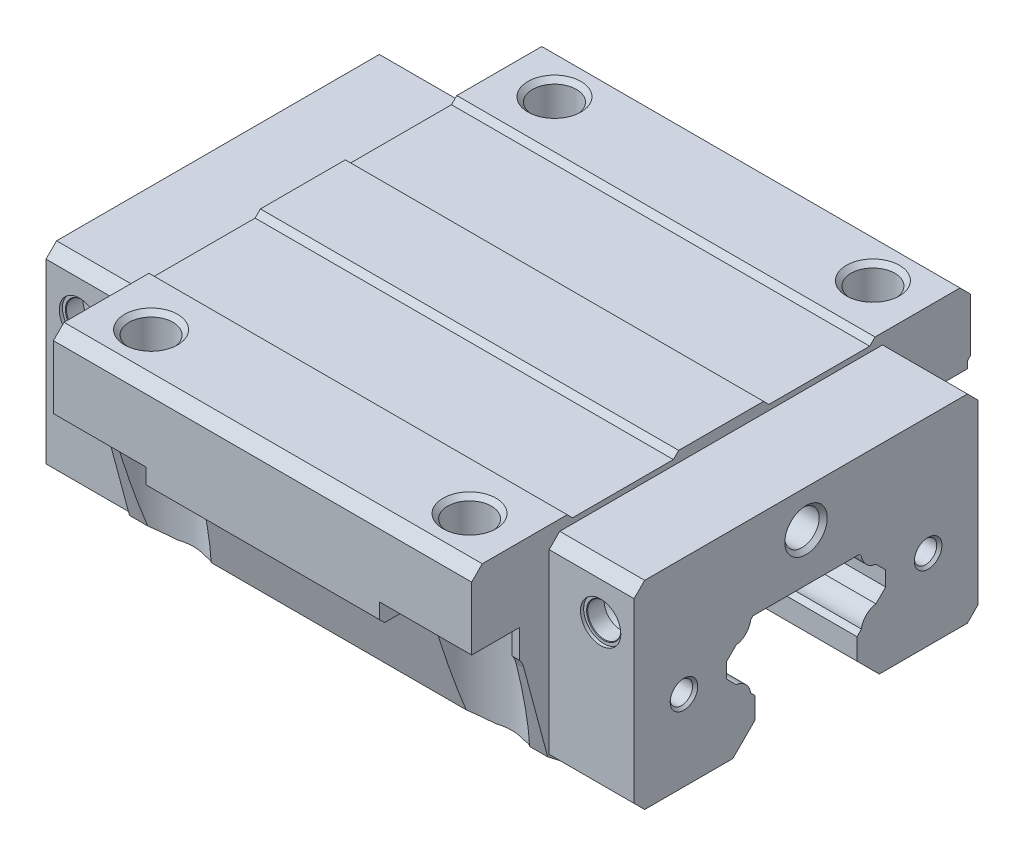
SolidWorks part; units mm, degrees
ref_plane "Спереди" through (0, 0, 0) normal (0, 0, 1) x (1, 0, 0)
ref_plane "Сверху" through (0, 0, 0) normal (0, 1, 0) x (1, 0, 0)
ref_plane "Сбоку" through (0, 0, 0) normal (1, 0, 0) x (0, 0, -1)
ref_plane "Плоскость1" through (0, 0, 0) normal (1, 0, 0) x (0, 0, -1)
sketch "Эскиз1" plane through (0, 0, 0) normal (1, 0, 0) x (0, 0, -1)
  line L0 (-23.5, 18.703) -> (-23.5, 11.2985)
  line L1 (-23.5, 11.2985) -> (-23.0015, 10.8)
  line L2 (-23.0015, 10.8) -> (-20.5347, 10.8)
  line L3 (-18.6028, 9.3176) -> (-16.3361, 0.8584)
  line L4 (-16.3361, 0.8584) -> (-15.2175, 0)
  line L5 (-15.2175, 0) -> (15.2175, 0)
  line L6 (15.2175, 0) -> (16.3361, 0.8584)
  line L7 (16.3361, 0.8584) -> (18.6028, 9.3176)
  line L8 (20.5347, 10.8) -> (22.7015, 10.8)
  line L9 (22.7015, 10.8) -> (23.2, 11.2985)
  line L10 (23.2, 11.2985) -> (23.2, 13.4)
  line L11 (23.2, 13.4) -> (23.5, 13.7)
  line L12 (23.5, 13.7) -> (23.5, 18.703)
  line L13 (23.5, 18.703) -> (22.503, 19.7)
  line L14 (22.503, 19.7) -> (14.5, 19.7)
  line L15 (14.5, 19.7) -> (14, 19.2)
  line L16 (14, 19.2) -> (4.5, 19.2)
  line L17 (4.5, 19.2) -> (4, 19.7)
  line L18 (4, 19.7) -> (-4, 19.7)
  line L19 (-4, 19.7) -> (-4.5, 19.2)
  line L20 (-4.5, 19.2) -> (-14, 19.2)
  line L21 (-14, 19.2) -> (-14.5, 19.7)
  line L22 (-14.5, 19.7) -> (-22.503, 19.7)
  line L23 (-22.503, 19.7) -> (-23.5, 18.703)
  arc A0 (-20.5347, 10.8) -> (-18.6028, 9.3176) centre (-20.5347, 8.8) cw
  arc A1 (18.6028, 9.3176) -> (20.5347, 10.8) centre (20.5347, 8.8) cw
extrude "Бобышка-Вытянуть1" add sketch "Эскиз1" against normal blind 19.7 and the other way blind 19.7
ref_plane "Плоскость2" through (0, 0, 0) normal (1, 0, 0) x (0, 0, -1)
sketch "Эскиз2" plane through (0, 0, 0) normal (1, 0, 0) x (0, 0, -1)
  line L0 (-16.2, 0.997) -> (-15.203, 0)
  line L1 (-15.203, 0) -> (15.203, 0)
  line L2 (15.203, 0) -> (16.2, 0.997)
  line L3 (16.2, 0.997) -> (16.2, 17.703)
  line L4 (16.2, 17.703) -> (15.203, 18.7)
  line L5 (15.203, 18.7) -> (-15.203, 18.7)
  line L6 (-15.203, 18.7) -> (-16.2, 17.703)
  line L7 (-16.2, 17.703) -> (-16.2, 0.997)
extrude "Бобышка-Вытянуть2" add sketch "Эскиз2" against normal blind 27.7 and the other way blind 27.7
ref_plane "Плоскость3" through (0, 0, 0) normal (1, 0, 0) x (0, 0, -1)
sketch "Эскиз3" plane through (0, 0, 0) normal (1, 0, 0) x (0, 0, -1)
  line L0 (-11.2, -4.3) -> (11.2, -4.3)
  line L1 (11.2, -4.3) -> (4.8, 2.1)
  line L2 (4.8, 2.1) -> (4.8, 4.1)
  line L3 (4.8, 4.1) -> (5.2144, 4.5144)
  line L4 (6.5856, 5.8856) -> (7.5, 6.8)
  line L5 (7.5, 6.8) -> (7.5, 8.2)
  line L6 (7.5, 8.2) -> (6.5856, 9.1144)
  line L7 (5.2144, 10.4856) -> (5, 10.7)
  line L8 (5, 10.7) -> (-5, 10.7)
  line L9 (-5, 10.7) -> (-5.2144, 10.4856)
  line L10 (-6.5856, 9.1144) -> (-7.5, 8.2)
  line L11 (-7.5, 8.2) -> (-7.5, 6.8)
  line L12 (-7.5, 6.8) -> (-6.5856, 5.8856)
  line L13 (-5.2144, 4.5144) -> (-4.8, 4.1)
  line L14 (-4.8, 4.1) -> (-4.8, 2.1)
  line L15 (-4.8, 2.1) -> (-11.2, -4.3)
  arc A0 (5.2144, 4.5144) -> (6.5856, 5.8856) centre (6.8, 4.3) cw
  arc A1 (6.5856, 9.1144) -> (5.2144, 10.4856) centre (6.8, 10.7) cw
  arc A2 (-5.2144, 10.4856) -> (-6.5856, 9.1144) centre (-6.8, 10.7) cw
  arc A3 (-6.5856, 5.8856) -> (-5.2144, 4.5144) centre (-6.8, 4.3) cw
extrude "Вырез-Вытянуть1" cut sketch "Эскиз3" against normal blind 19.7 and the other way blind 19.7
ref_plane "Плоскость4" through (19.7, 0, 0) normal (1, 0, 0) x (0, 0, -1)
sketch "Эскиз4" plane through (19.7, 0, 0) normal (1, 0, 0) x (0, 0, -1)
  line L0 (-11.2, -4.3) -> (11.2, -4.3)
  line L1 (11.2, -4.3) -> (4.8, 2.1)
  line L2 (4.8, 2.1) -> (4.8, 4.1)
  line L3 (4.8, 4.1) -> (5.2144, 4.5144)
  line L4 (6.5856, 5.8856) -> (7.5, 6.8)
  line L5 (7.5, 6.8) -> (7.5, 8.2)
  line L6 (7.5, 8.2) -> (6.5856, 9.1144)
  line L7 (5.2144, 10.4856) -> (5, 10.7)
  line L8 (5, 10.7) -> (-5, 10.7)
  line L9 (-5, 10.7) -> (-5.2144, 10.4856)
  line L10 (-6.5856, 9.1144) -> (-7.5, 8.2)
  line L11 (-7.5, 8.2) -> (-7.5, 6.8)
  line L12 (-7.5, 6.8) -> (-6.5856, 5.8856)
  line L13 (-5.2144, 4.5144) -> (-4.8, 4.1)
  line L14 (-4.8, 4.1) -> (-4.8, 2.1)
  line L15 (-4.8, 2.1) -> (-11.2, -4.3)
  arc A0 (5.2144, 4.5144) -> (6.5856, 5.8856) centre (6.8, 4.3) cw
  arc A1 (6.5856, 9.1144) -> (5.2144, 10.4856) centre (6.8, 10.7) cw
  arc A2 (-5.2144, 10.4856) -> (-6.5856, 9.1144) centre (-6.8, 10.7) cw
  arc A3 (-6.5856, 5.8856) -> (-5.2144, 4.5144) centre (-6.8, 4.3) cw
extrude "Вырез-Вытянуть2" cut sketch "Эскиз4" along normal blind 19.7
ref_plane "Плоскость5" through (-19.7, 0, 0) normal (1, 0, 0) x (0, 0, -1)
sketch "Эскиз5" plane through (-19.7, 0, 0) normal (1, 0, 0) x (0, 0, -1)
  line L0 (-11.2, -4.3) -> (11.2, -4.3)
  line L1 (11.2, -4.3) -> (4.8, 2.1)
  line L2 (4.8, 2.1) -> (4.8, 4.1)
  line L3 (4.8, 4.1) -> (5.2144, 4.5144)
  line L4 (6.5856, 5.8856) -> (7.5, 6.8)
  line L5 (7.5, 6.8) -> (7.5, 8.2)
  line L6 (7.5, 8.2) -> (6.5856, 9.1144)
  line L7 (5.2144, 10.4856) -> (5, 10.7)
  line L8 (5, 10.7) -> (-5, 10.7)
  line L9 (-5, 10.7) -> (-5.2144, 10.4856)
  line L10 (-6.5856, 9.1144) -> (-7.5, 8.2)
  line L11 (-7.5, 8.2) -> (-7.5, 6.8)
  line L12 (-7.5, 6.8) -> (-6.5856, 5.8856)
  line L13 (-5.2144, 4.5144) -> (-4.8, 4.1)
  line L14 (-4.8, 4.1) -> (-4.8, 2.1)
  line L15 (-4.8, 2.1) -> (-11.2, -4.3)
  arc A0 (5.2144, 4.5144) -> (6.5856, 5.8856) centre (6.8, 4.3) cw
  arc A1 (6.5856, 9.1144) -> (5.2144, 10.4856) centre (6.8, 10.7) cw
  arc A2 (-5.2144, 10.4856) -> (-6.5856, 9.1144) centre (-6.8, 10.7) cw
  arc A3 (-6.5856, 5.8856) -> (-5.2144, 4.5144) centre (-6.8, 4.3) cw
extrude "Вырез-Вытянуть3" cut sketch "Эскиз5" against normal blind 19.7
ref_plane "Плоскость6" through (0, 0, -19) normal (0, 0, 1) x (1, 0, 0)
sketch "Эскиз6" plane through (0, 0, -19) normal (0, 0, 1) x (1, 0, 0)
  line L0 (15, 19.7) -> (17.5, 19.7)
  line L1 (17.5, 19.7) -> (17.067, 19.267)
  line L2 (17.067, 19.267) -> (17.067, 13.183)
  line L3 (17.067, 13.183) -> (17.5, 12.75)
  line L4 (17.5, 12.75) -> (17.5, 0)
  line L5 (17.5, 0) -> (15, 0)
  line L6 (15, 0) -> (15, 19.7)
  line L7 (15, 0) -> (15, 19.7) construction
revolve "Вырез-Повернуть1" cut sketch "Эскиз6" angle 360 about L7 reverse direction yes
ref_plane "Плоскость7" through (0, 0, -19) normal (0, 0, 1) x (1, 0, 0)
sketch "Эскиз7" plane through (0, 0, -19) normal (0, 0, 1) x (1, 0, 0)
  line L0 (-15, 19.7) -> (-12.5, 19.7)
  line L1 (-12.5, 19.7) -> (-12.933, 19.267)
  line L2 (-12.933, 19.267) -> (-12.933, 13.183)
  line L3 (-12.933, 13.183) -> (-12.5, 12.75)
  line L4 (-12.5, 12.75) -> (-12.5, 0)
  line L5 (-12.5, 0) -> (-15, 0)
  line L6 (-15, 0) -> (-15, 19.7)
  line L7 (-15, 0) -> (-15, 19.7) construction
revolve "Вырез-Повернуть2" cut sketch "Эскиз7" angle 360 about L7 reverse direction yes
ref_plane "Плоскость8" through (0, 0, 19) normal (0, 0, 1) x (1, 0, 0)
sketch "Эскиз8" plane through (0, 0, 19) normal (0, 0, 1) x (1, 0, 0)
  line L0 (15, 19.7) -> (17.5, 19.7)
  line L1 (17.5, 19.7) -> (17.067, 19.267)
  line L2 (17.067, 19.267) -> (17.067, 13.183)
  line L3 (17.067, 13.183) -> (17.5, 12.75)
  line L4 (17.5, 12.75) -> (17.5, 0)
  line L5 (17.5, 0) -> (15, 0)
  line L6 (15, 0) -> (15, 19.7)
  line L7 (15, 0) -> (15, 19.7) construction
revolve "Вырез-Повернуть3" cut sketch "Эскиз8" angle 360 about L7 reverse direction yes
ref_plane "Плоскость9" through (0, 0, 19) normal (0, 0, 1) x (1, 0, 0)
sketch "Эскиз9" plane through (0, 0, 19) normal (0, 0, 1) x (1, 0, 0)
  line L0 (-15, 19.7) -> (-12.5, 19.7)
  line L1 (-12.5, 19.7) -> (-12.933, 19.267)
  line L2 (-12.933, 19.267) -> (-12.933, 13.183)
  line L3 (-12.933, 13.183) -> (-12.5, 12.75)
  line L4 (-12.5, 12.75) -> (-12.5, 0)
  line L5 (-12.5, 0) -> (-15, 0)
  line L6 (-15, 0) -> (-15, 19.7)
  line L7 (-15, 0) -> (-15, 19.7) construction
revolve "Вырез-Повернуть4" cut sketch "Эскиз9" angle 360 about L7 reverse direction yes
ref_plane "Плоскость10" through (0, 0, 0) normal (0, 0, 1) x (1, 0, 0)
sketch "Эскиз10" plane through (0, 0, 0) normal (0, 0, 1) x (1, 0, 0)
  line L0 (-27.7, 15.2) -> (-27.7, 17.2)
  line L1 (-27.7, 17.2) -> (-27.321, 16.821)
  line L2 (-27.321, 16.821) -> (-18.6359, 16.821)
  line L3 (-18.6359, 16.821) -> (-17.7, 15.2)
  line L4 (-17.7, 15.2) -> (-27.7, 15.2)
  line L5 (-17.7, 15.2) -> (-27.7, 15.2) construction
revolve "Вырез-Повернуть5" cut sketch "Эскиз10" angle 360 about L5 reverse direction yes
ref_plane "Плоскость11" through (24.55, 0, 0) normal (1, 0, 0) x (0, 0, -1)
sketch "Эскиз11" plane through (24.55, 0, 0) normal (1, 0, 0) x (0, 0, -1)
  line L0 (-16.2, 14.2) -> (-16.2, 16.1)
  line L1 (-16.2, 16.1) -> (-15.9, 16.1)
  line L2 (-15.9, 16.1) -> (-15.9, 15.823)
  line L3 (-15.9, 15.823) -> (-15.847, 15.77)
  line L4 (-15.847, 15.77) -> (-14.3, 15.77)
  line L5 (-14.3, 15.77) -> (-13.8266, 14.95)
  line L6 (-13.8266, 14.95) -> (-13.8266, 14.2)
  line L7 (-13.8266, 14.2) -> (-16.2, 14.2)
  line L8 (-13.8266, 14.2) -> (-16.2, 14.2) construction
revolve "Вырез-Повернуть6" cut sketch "Эскиз11" angle 360 about L8 reverse direction yes
ref_plane "Плоскость12" through (-24.55, 0, 0) normal (1, 0, 0) x (0, 0, -1)
sketch "Эскиз12" plane through (-24.55, 0, 0) normal (1, 0, 0) x (0, 0, -1)
  line L0 (-16.2, 14.2) -> (-16.2, 16.1)
  line L1 (-16.2, 16.1) -> (-15.9, 16.1)
  line L2 (-15.9, 16.1) -> (-15.9, 15.823)
  line L3 (-15.9, 15.823) -> (-15.847, 15.77)
  line L4 (-15.847, 15.77) -> (-14.3, 15.77)
  line L5 (-14.3, 15.77) -> (-13.8266, 14.95)
  line L6 (-13.8266, 14.95) -> (-13.8266, 14.2)
  line L7 (-13.8266, 14.2) -> (-16.2, 14.2)
  line L8 (-13.8266, 14.2) -> (-16.2, 14.2) construction
revolve "Вырез-Повернуть7" cut sketch "Эскиз12" angle 360 about L8 reverse direction yes
ref_plane "Плоскость13" through (0, 0, 11.5) normal (0, 0, 1) x (1, 0, 0)
sketch "Эскиз13" plane through (0, 0, 11.5) normal (0, 0, 1) x (1, 0, 0)
  line L0 (-27.7, 7.5556) -> (-27.7, 8.8556)
  line L1 (-27.7, 8.8556) -> (-27.4565, 8.6121)
  line L2 (-27.4565, 8.6121) -> (-17.7, 8.6121)
  line L3 (-17.7, 8.6121) -> (-17.09, 7.5556)
  line L4 (-17.09, 7.5556) -> (-27.7, 7.5556)
  line L5 (-17.09, 7.5556) -> (-27.7, 7.5556) construction
revolve "Вырез-Повернуть8" cut sketch "Эскиз13" angle 360 about L5 reverse direction yes
ref_plane "Плоскость14" through (0, 0, 11.5) normal (0, 0, 1) x (1, 0, 0)
sketch "Эскиз14" plane through (0, 0, 11.5) normal (0, 0, 1) x (1, 0, 0)
  line L0 (17.09, 7.5556) -> (17.7, 8.6121)
  line L1 (17.7, 8.6121) -> (27.4565, 8.6121)
  line L2 (27.4565, 8.6121) -> (27.7, 8.8556)
  line L3 (27.7, 8.8556) -> (27.7, 7.5556)
  line L4 (27.7, 7.5556) -> (17.09, 7.5556)
  line L5 (27.7, 7.5556) -> (17.09, 7.5556) construction
revolve "Вырез-Повернуть9" cut sketch "Эскиз14" angle 360 about L5 reverse direction yes
ref_plane "Плоскость15" through (0, 0, -11.5) normal (0, 0, 1) x (1, 0, 0)
sketch "Эскиз15" plane through (0, 0, -11.5) normal (0, 0, 1) x (1, 0, 0)
  line L0 (-27.7, 7.5556) -> (-27.7, 8.8556)
  line L1 (-27.7, 8.8556) -> (-27.4565, 8.6121)
  line L2 (-27.4565, 8.6121) -> (-17.7, 8.6121)
  line L3 (-17.7, 8.6121) -> (-17.09, 7.5556)
  line L4 (-17.09, 7.5556) -> (-27.7, 7.5556)
  line L5 (-17.09, 7.5556) -> (-27.7, 7.5556) construction
revolve "Вырез-Повернуть10" cut sketch "Эскиз15" angle 360 about L5 reverse direction yes
ref_plane "Плоскость16" through (0, 0, -11.5) normal (0, 0, 1) x (1, 0, 0)
sketch "Эскиз16" plane through (0, 0, -11.5) normal (0, 0, 1) x (1, 0, 0)
  line L0 (17.09, 7.5556) -> (17.7, 8.6121)
  line L1 (17.7, 8.6121) -> (27.4565, 8.6121)
  line L2 (27.4565, 8.6121) -> (27.7, 8.8556)
  line L3 (27.7, 8.8556) -> (27.7, 7.5556)
  line L4 (27.7, 7.5556) -> (17.09, 7.5556)
  line L5 (27.7, 7.5556) -> (17.09, 7.5556) construction
revolve "Вырез-Повернуть11" cut sketch "Эскиз16" angle 360 about L5 reverse direction yes
ref_plane "Плоскость17" through (-24.55, 0, 0) normal (1, 0, 0) x (0, 0, -1)
sketch "Эскиз17" plane through (-24.55, 0, 0) normal (1, 0, 0) x (0, 0, -1)
  line L0 (13.8266, 14.2) -> (13.8266, 14.95)
  line L1 (13.8266, 14.95) -> (14.3, 15.77)
  line L2 (14.3, 15.77) -> (15.847, 15.77)
  line L3 (15.847, 15.77) -> (15.9, 15.823)
  line L4 (15.9, 15.823) -> (15.9, 16.1)
  line L5 (15.9, 16.1) -> (16.2, 16.1)
  line L6 (16.2, 16.1) -> (16.2, 14.2)
  line L7 (16.2, 14.2) -> (13.8266, 14.2)
  line L8 (16.2, 14.2) -> (13.8266, 14.2) construction
revolve "Вырез-Повернуть12" cut sketch "Эскиз17" angle 360 about L8 reverse direction yes
ref_plane "Плоскость18" through (24.55, 0, 0) normal (1, 0, 0) x (0, 0, -1)
sketch "Эскиз18" plane through (24.55, 0, 0) normal (1, 0, 0) x (0, 0, -1)
  line L0 (13.8266, 14.2) -> (13.8266, 14.95)
  line L1 (13.8266, 14.95) -> (14.3, 15.77)
  line L2 (14.3, 15.77) -> (15.847, 15.77)
  line L3 (15.847, 15.77) -> (15.9, 15.823)
  line L4 (15.9, 15.823) -> (15.9, 16.1)
  line L5 (15.9, 16.1) -> (16.2, 16.1)
  line L6 (16.2, 16.1) -> (16.2, 14.2)
  line L7 (16.2, 14.2) -> (13.8266, 14.2)
  line L8 (16.2, 14.2) -> (13.8266, 14.2) construction
revolve "Вырез-Повернуть13" cut sketch "Эскиз18" angle 360 about L8 reverse direction yes
ref_plane "Плоскость19" through (0, 0, 0) normal (0, 0, 1) x (1, 0, 0)
sketch "Эскиз19" plane through (0, 0, 0) normal (0, 0, 1) x (1, 0, 0)
  line L0 (17.7, 15.2) -> (18.6359, 16.821)
  line L1 (18.6359, 16.821) -> (27.321, 16.821)
  line L2 (27.321, 16.821) -> (27.7, 17.2)
  line L3 (27.7, 17.2) -> (27.7, 15.2)
  line L4 (27.7, 15.2) -> (17.7, 15.2)
  line L5 (27.7, 15.2) -> (17.7, 15.2) construction
revolve "Вырез-Повернуть14" cut sketch "Эскиз19" angle 360 about L5 reverse direction yes
ref_plane "Плоскость20" through (0, 12.75, 0) normal (0, 1, 0) x (1, 0, 0)
sketch "Эскиз20" plane through (0, 12.75, 0) normal (0, 1, 0) x (1, 0, 0)
  line L0 (-27, -38) -> (27, -38)
  line L1 (27, -38) -> (27, -19)
  line L2 (27, -19) -> (19, -19)
  line L3 (11, -19) -> (11, -30.4)
  line L4 (11, -30.4) -> (-11, -30.4)
  line L5 (-11, -30.4) -> (-11, -19)
  line L6 (-19, -19) -> (-27, -19)
  line L7 (-27, -19) -> (-27, -38)
  arc A0 (19, -19) -> (11, -19) centre (15, -19) ccw
  arc A1 (-11, -19) -> (-19, -19) centre (-15, -19) ccw
extrude "Вырез-Вытянуть4" cut sketch "Эскиз20" against normal blind 19.7
ref_plane "Плоскость21" through (0, 12.75, 0) normal (0, 1, 0) x (1, 0, 0)
sketch "Эскиз21" plane through (0, 12.75, 0) normal (0, 1, 0) x (1, 0, 0)
  line L0 (-27, 38) -> (-27, 19)
  line L1 (-27, 19) -> (-19, 19)
  line L2 (-11, 19) -> (-11, 30.4)
  line L3 (-11, 30.4) -> (11, 30.4)
  line L4 (11, 30.4) -> (11, 19)
  line L5 (19, 19) -> (27, 19)
  line L6 (27, 19) -> (27, 38)
  line L7 (27, 38) -> (-27, 38)
  arc A0 (-19, 19) -> (-11, 19) centre (-15, 19) ccw
  arc A1 (11, 19) -> (19, 19) centre (15, 19) ccw
extrude "Вырез-Вытянуть5" cut sketch "Эскиз21" against normal blind 19.7
